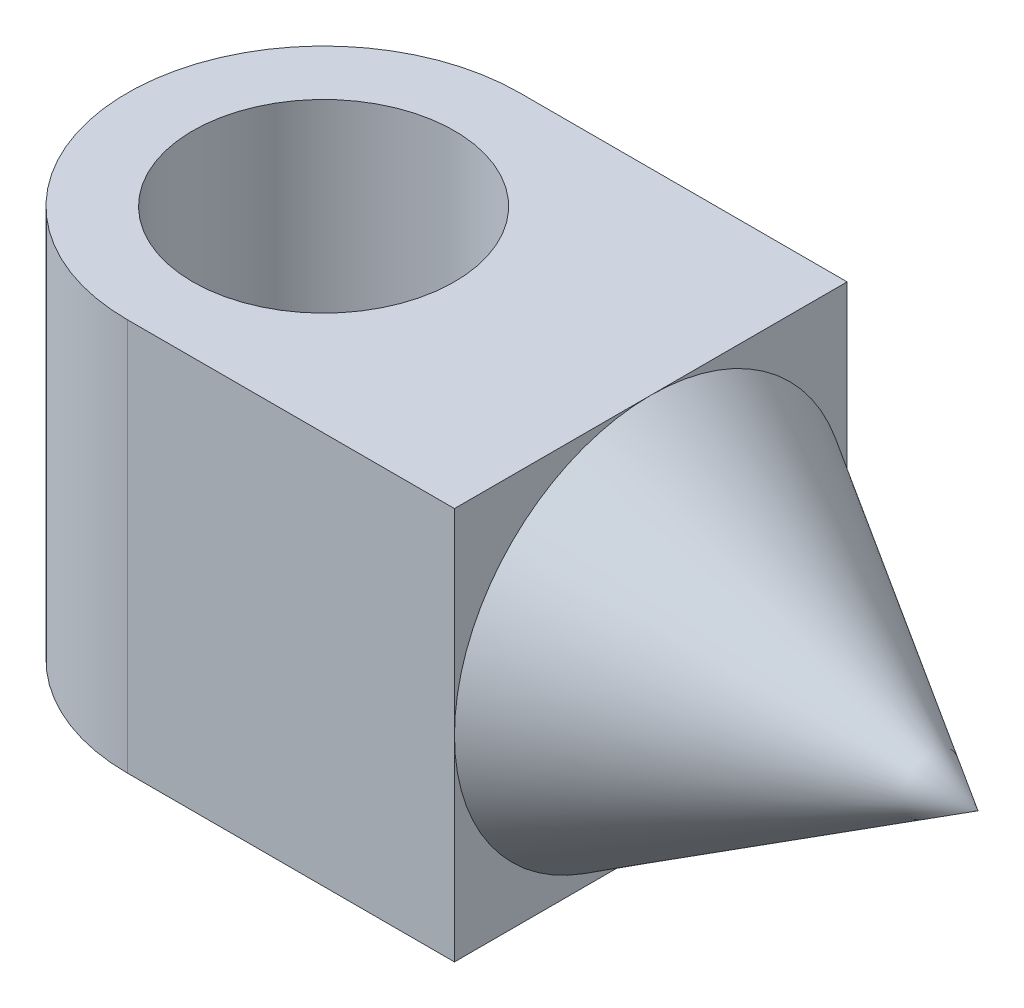
SolidWorks part; units mm, degrees
ref_plane "Front Plane" through (0, 0, 0) normal (0, 0, 1) x (1, 0, 0)
ref_plane "Top Plane" through (0, 0, 0) normal (0, 1, 0) x (1, 0, 0)
ref_plane "Right Plane" through (0, 0, 0) normal (1, 0, 0) x (0, 0, -1)
sketch "Sketch1" plane through (0, 0, 0) normal (0, 1, 0) x (1, 0, 0)
  line L2 (0, 15) -> (0, -15) construction
  line L3 (-25, 15) -> (0, 15)
  line L4 (-25, -15) -> (0, -15)
  line L5 (0, -15) -> (0, 15)
  line L6 (0, 15) -> (25, 0)
  line L7 (25, 0) -> (0, -15)
  line L8 (0, 0) -> (25, 0)
  circle A0 centre (-25, 0) radius 10
  arc A1 (-25, 15) -> (-25, -15) centre (-25, 0) ccw
  dimension "D1" = 20
  dimension "D2" = 15
  dimension "D3" = 25
extrude "Boss-Extrude2" add sketch "Sketch1" along normal blind 15 and the other way blind 15 contours L3 A1 L4 L5 A0 region at (-12.5, 0, -14.5)
revolve "Revolve2" add sketch "Sketch1<4>" angle 360 about L8 region at (8.3333, 0, -5)
sketch "Sketch1<4>" plane through (0, 0, 0) normal (0, 1, 0) x (1, 0, 0) same geometry as "Sketch1"
